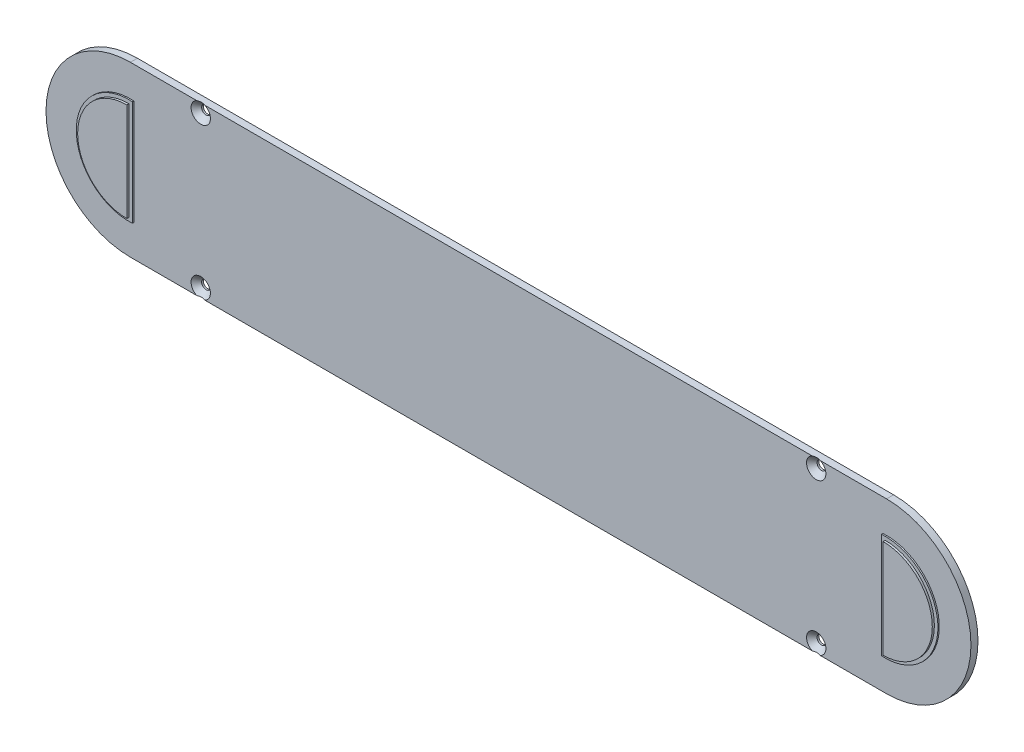
SolidWorks part; units mm, degrees
material "AISI 316L Acero inoxidable"
ref_plane "Alzado" through (0, 0, 0) normal (0, 0, 1) x (1, 0, 0)
ref_plane "Planta" through (0, 0, 0) normal (0, 1, 0) x (1, 0, 0)
ref_plane "Vista lateral" through (0, 0, 0) normal (1, 0, 0) x (0, 0, -1)
sketch "Croquis2" plane through (0, 0, 2) normal (0, 0, 1) x (1, 0, 0)
  line L2 (-107.5, -24) -> (107.5, -24)
  line L3 (107.5, 24) -> (-107.5, 24)
  circle A6 centre (-87.5, -21.5) radius 1.25
  arc A7 (-107.5, 24) -> (-107.5, -24) centre (-107.5, 0) ccw
  circle A8 centre (-87.5, 21.5) radius 1.25
  circle A9 centre (87.5, 21.5) radius 1.25
  circle A10 centre (87.5, -21.5) radius 1.25
  arc A11 (107.5, -24) -> (107.5, 24) centre (107.5, 0) ccw
  dimension "D1" = 2.5
  dimension "D2" = 24
  dimension "D3" = 87.5
  dimension "D4" = 107.5
  dimension "D5" = 87.5
  dimension "D6" = 107.5
  dimension "D7" = 21.5
  dimension "D8" = 21.5
extrude "Saliente-Extruir1" add sketch "Croquis2" against normal blind 2
chamfer "Chaflán1" distance 1.5 angle 45 4 edges at (88.75, 21.5, 2) (88.75, -21.5, 2) (-86.25, -21.5, 2) (-86.25, 21.5, 2)
sketch "Croquis3" plane through (0, 0, 2) normal (0, 0, 1) x (1, 0, 0)
  line L0 (-107.5, 14) -> (-107.5, -14)
  line L1 (107.5, 14) -> (107.5, -14)
  arc A0 (-107.5, 24) -> (-107.5, -24) centre (-107.5, 0) ccw construction
  arc A1 (107.5, -24) -> (107.5, 24) centre (107.5, 0) ccw construction
  arc A2 (-107.5, 24) -> (-107.5, -24) centre (-107.5, 0) ccw construction
  arc A3 (107.5, -24) -> (107.5, 24) centre (107.5, 0) ccw construction
  arc A4 (-107.5, 14) -> (-107.5, -14) centre (-107.5, 0) ccw
  arc A5 (107.5, -14) -> (107.5, 14) centre (107.5, 0) ccw
  dimension "D1" = 10
extrude "Saliente-Extruir2" add sketch "Croquis3" along normal blind 1
sketch "Croquis4" plane through (0, 0, 2) normal (0, 0, 1) x (1, 0, 0)
  line L0 (-107.5, -14) -> (-107.5, 14) construction
  line L1 (107.5, 14) -> (107.5, -14) construction
  line L2 (-107.5, -14) -> (-107.5, 14)
  line L3 (107.5, 14) -> (107.5, -14)
  line L4 (-106.5, -14.9666) -> (-106.5, 14.9666)
  line L5 (106.5, 14.9666) -> (106.5, -14.9666)
  arc A0 (-107.5, 14) -> (-107.5, -14) centre (-107.5, 0) ccw construction
  arc A1 (107.5, -14) -> (107.5, 14) centre (107.5, 0) ccw construction
  arc A2 (-107.5, 14) -> (-107.5, -14) centre (-107.5, 0) ccw
  arc A3 (107.5, -14) -> (107.5, 14) centre (107.5, 0) ccw
  arc A4 (-106.5, 14.9666) -> (-106.5, -14.9666) centre (-107.5, 0) ccw
  arc A5 (106.5, -14.9666) -> (106.5, 14.9666) centre (107.5, 0) ccw
  dimension "D1" = 1
extrude "Saliente-Extruir3" add sketch "Croquis4" along normal blind 0.4
